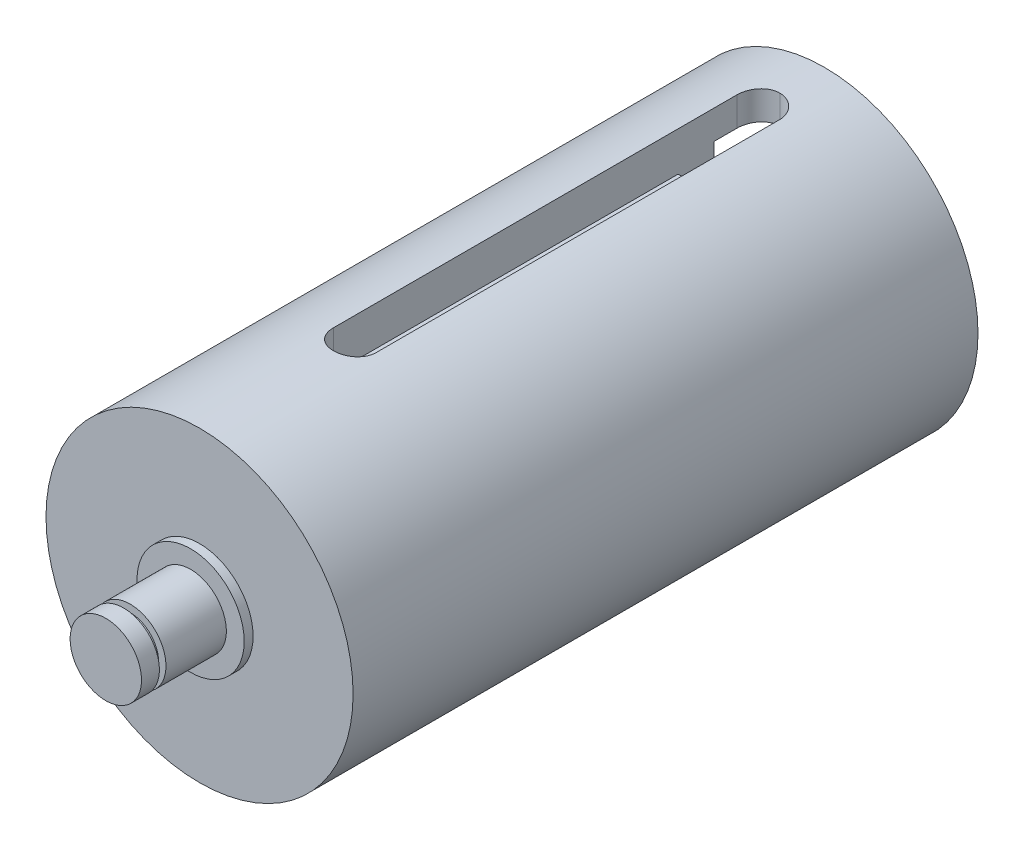
SolidWorks part; units mm, degrees
ref_plane "Front" through (0, 0, 0) normal (0, 0, 1) x (1, 0, 0)
ref_plane "Top" through (0, 0, 0) normal (0, 1, 0) x (1, 0, 0)
ref_plane "Right" through (0, 0, 0) normal (1, 0, 0) x (0, 0, -1)
sketch "Sketch1" plane through (0, 0, 0) normal (0, 0, 1) x (1, 0, 0)
  circle A0 centre (0, 0) radius 17.2
extrude "Boss-Extrude1" add sketch "Sketch1" along normal blind 70
sketch "Sketch2" plane through (0, 0, 0) normal (0, 0, -1) x (-1, 0, 0)
  circle A0 centre (0, 0) radius 14
extrude "Cut-Extrude1" cut sketch "Sketch2" against normal blind 14
sketch "Sketch3" plane through (0, 0, 14) normal (0, 0, -1) x (-1, 0, 0)
  circle A0 centre (0, 0) radius 8.25
extrude "Cut-Extrude2" cut sketch "Sketch3" against normal blind 50
sketch "Sketch4" plane through (0, 0, 0) normal (0, 1, 0) x (1, 0, 0)
  line L0 (0, -41.3382) -> (0, -82.5078) construction
  line L1 (8.25, -64) -> (0, -66)
  line L2 (0, -66) -> (0, -64)
  line L3 (8.25, -64) -> (-8.25, -64) construction
  line L4 (0, -64) -> (8.25, -64)
revolve "Cut-Revolve1" cut sketch "Sketch4" angle 360 about L2
sketch "Sketch5" plane through (0, 0, 70) normal (0, 0, 1) x (1, 0, 0)
  circle A0 centre (0, 0) radius 4
extrude "Boss-Extrude2" add sketch "Sketch5" along normal blind 10.5
sketch "Sketch9" plane through (0, 0, 14) normal (0, 0, -1) x (-1, 0, 0)
  line L1 (-14, 0) -> (-7, -12.1244)
  line L2 (-7, -12.1244) -> (7, -12.1244)
  line L3 (7, -12.1244) -> (14, 0)
  line L4 (14, 0) -> (7, 12.1244)
  line L5 (7, 12.1244) -> (-7, 12.1244)
  line L6 (-7, 12.1244) -> (-14, 0)
  circle A0 centre (0, 0) radius 12.1244 construction
  circle A1 centre (0, 0) radius 16.3795
extrude "Boss-Extrude4" add sketch "Sketch9" along normal blind 4
sketch "Sketch6" plane through (0, 0, 0) normal (0, 0, -1) x (-1, 0, 0)
  line L0 (0, 18.5132) -> (0, -18.5132) construction
  line L1 (19.2798, 0) -> (-21.0451, 0) construction
  line L2 (-2.4, 17.0317) -> (-2.4, 12.6317)
  line L3 (-2.4, 12.6317) -> (2.4, 12.6317)
  line L4 (2.4, 12.6317) -> (2.4, 17.0317)
  circle A0 centre (0, 0) radius 17.2 construction
  arc A1 (-2.4, 17.0317) -> (2.4, 17.0317) centre (0, 0) cw
  dimension "D1" = 2.4
extrude "Cut-Extrude3" cut sketch "Sketch6" against normal blind 50 from offset 5 offset against normal yes
fillet "Fillet2" radius 2.4 4 edges at (-2.4, 14.8317, 55) (2.4, 14.8317, 55) (-2.4, 15.4122, 5) (2.4, 15.4122, 5)
sketch "Sketch7" plane through (0, 0, 70) normal (0, 0, 1) x (1, 0, 0)
  circle A0 centre (0, 0) radius 6
extrude "Boss-Extrude3" add sketch "Sketch7" along normal blind 1
sketch "Sketch8" plane through (0, 0, 80.5) normal (0, 0, 1) x (1, 0, 0)
  circle A0 centre (0, 0) radius 3.175
  circle A1 centre (0, 0) radius 4.2633
extrude "Cut-Extrude4" cut sketch "Sketch8" against normal blind 0.74 from offset 2 offset against normal yes
sketch "Sketch10" plane through (0, 12.1244, 0) normal (0, -1, 0) x (1, 0, 0)
  line L0 (2.4, 10) -> (2.4, 14)
  line L1 (2.4, 52.6) -> (2.4, 7.4) construction
  line L2 (2.4, 14) -> (-2.4, 14)
  line L3 (-2.4, 52.6) -> (-2.4, 10) construction
  line L4 (-2.4, 14) -> (-2.4, 10)
  line L5 (-2.4, 10) -> (2.4, 10)
extrude "Cut-Extrude5" cut sketch "Sketch10" against normal blind 10
